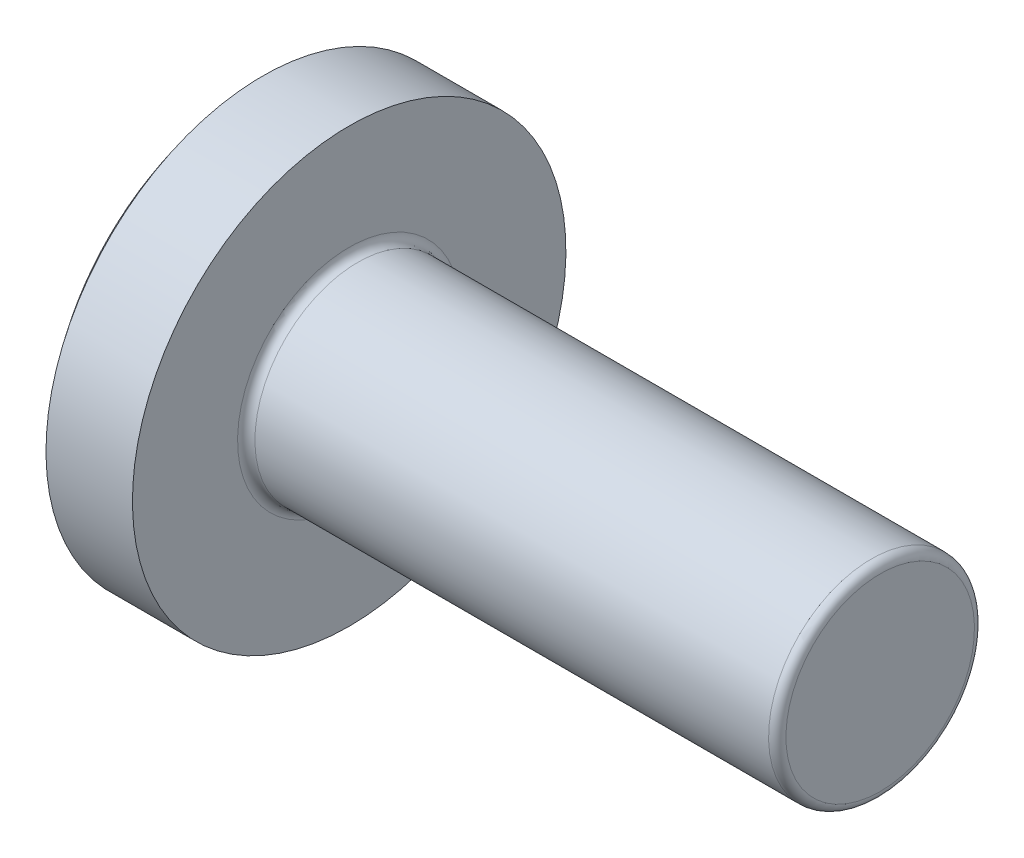
SolidWorks part; units mm, degrees
ref_plane "Front" through (0, 0, 0) normal (0, 0, 1) x (1, 0, 0)
ref_plane "Top" through (0, 0, 0) normal (0, 1, 0) x (1, 0, 0)
ref_plane "Right" through (0, 0, 0) normal (1, 0, 0) x (0, 0, -1)
sketch "Sketch1" plane through (0, 0, 0) normal (0, 0, 1) x (1, 0, 0)
  line L0 (-8.6356, 0) -> (8.9, 0) construction
  line L1 (32, 0) -> (32, 4.75)
  line L2 (32, 4.75) -> (7.5, 4.75)
  line L3 (7.5, 4.75) -> (7.5, 10)
  line L4 (7.5, 10) -> (3.51, 10)
  line L5 (32, 0) -> (0, 0)
  arc A0 (3.51, 10) -> (0, 0) centre (16, 0) ccw
  dimension "l" = 24.5
revolve "Base" add sketch "Sketch1" angle 360 about L0
cosmetic thread "ThreadCosmetic1" [suppressed] parameters "D1"=23.1, "D2"=7.6
sketch "Sketch2" plane through (0, 0, 0) normal (1, 0, 0) x (0, 0, -1)
  line L0 (6.5369, 0) -> (-7.0008, 0) construction
  line L1 (0, 6.811) -> (0, -6.4314) construction
  line L2 (-1.01, 5.05) -> (1.01, 5.05)
  line L3 (1.01, 5.05) -> (1.01, 1.01)
  line L4 (1.01, 1.01) -> (5.05, 1.01)
  line L5 (5.05, 1.01) -> (5.05, -1.01)
  line L6 (1.01, -1.01) -> (5.05, -1.01)
  line L7 (1.01, -5.05) -> (1.01, -1.01)
  line L8 (-1.01, -5.05) -> (1.01, -5.05)
  line L9 (-1.01, -5.05) -> (-1.01, -1.01)
  line L10 (-1.01, -1.01) -> (-5.05, -1.01)
  line L11 (-5.05, 1.01) -> (-5.05, -1.01)
  line L12 (-1.01, 1.01) -> (-5.05, 1.01)
  line L13 (-1.01, 5.05) -> (-1.01, 1.01)
  point P5 (-5.05, 0)
  point P11 (5.05, 0)
  point P15 (0, -5.05)
  point P20 (0, 5.05)
  dimension "D2" = 10.1
  dimension "D3" = 2.02
  dimension "D4" = 2.02
extrude "Cut-Extrude1" cut sketch "Sketch2" along normal blind 5.2
fillet "Fillet1" radius 0.4 2 edges at (7.5, -4.75, 0) (32, -4.75, 0)
draft "Draft1" type of draft neutral plane draft angle 30 neutral plane "Right" faces to draft 4 face at (3.0173, 5.05, 0) face at (3.0173, 0, 5.05) face at (3.0173, -5.05, 0) face at (3.0173, 0, -5.05) neutral plane through (0, 0, 0) neutral plane normal (1, 0, 0) reverse direction yes parameters "D1"=30
sketch "Sketch3" plane through (0, 0, 0) normal (0, 0, 1) x (1, 0, 0)
  line L0 (8.425, 5.7) -> (9.375, 5.7)
  line L1 (9.375, 5.7) -> (9.375, 4.75)
  line L2 (9.375, 4.75) -> (8.9, 3.9273)
  line L3 (8.9, 3.9273) -> (8.425, 4.75)
  line L4 (8.425, 4.75) -> (8.425, 5.7)
  line L5 (0, 0) -> (33.8691, 0) construction
  line L6 (7.5, -10) -> (7.5, 10) construction
  dimension "D1" = 9.5
  dimension "D2" = 0.95
  dimension "D3" = 1.4
revolve "Cut-Revolve10" [suppressed] cut sketch "Sketch3" angle 360 about L5
pattern_linear "LPattern10" [suppressed] count 20 spacing 1.14 along (1, 0, 0) of bodies 103
equation "\"D3@Sketch2\" = \"m@Sketch2\" / 5"
equation "\"D4@Sketch2\" = \"D3@Sketch2\""
equation "\"D2@Sketch2\" = \"m@Sketch2\""
equation "\"D2@ThreadCosmetic1\" = \"st@Sketch1\"  * 4 / 5"
equation "\"D1@ThreadCosmetic1\" = \"l@Sketch1\" - \"a@Sketch1\""
equation "\"D1@Sketch3\" = \"st@Sketch1\""
equation "\"D2@Sketch3\" = (  \"st@Sketch1\" - \"D2@ThreadCosmetic1\" )  / 2"
equation "\"D3@Sketch3\" = \"a@Sketch1\""
equation "\"D3@LPattern10\" = \"D2@Sketch3\" * 1.2"
equation "\"D1@LPattern10\" = \"D1@ThreadCosmetic1\" / \"D3@LPattern10\""
